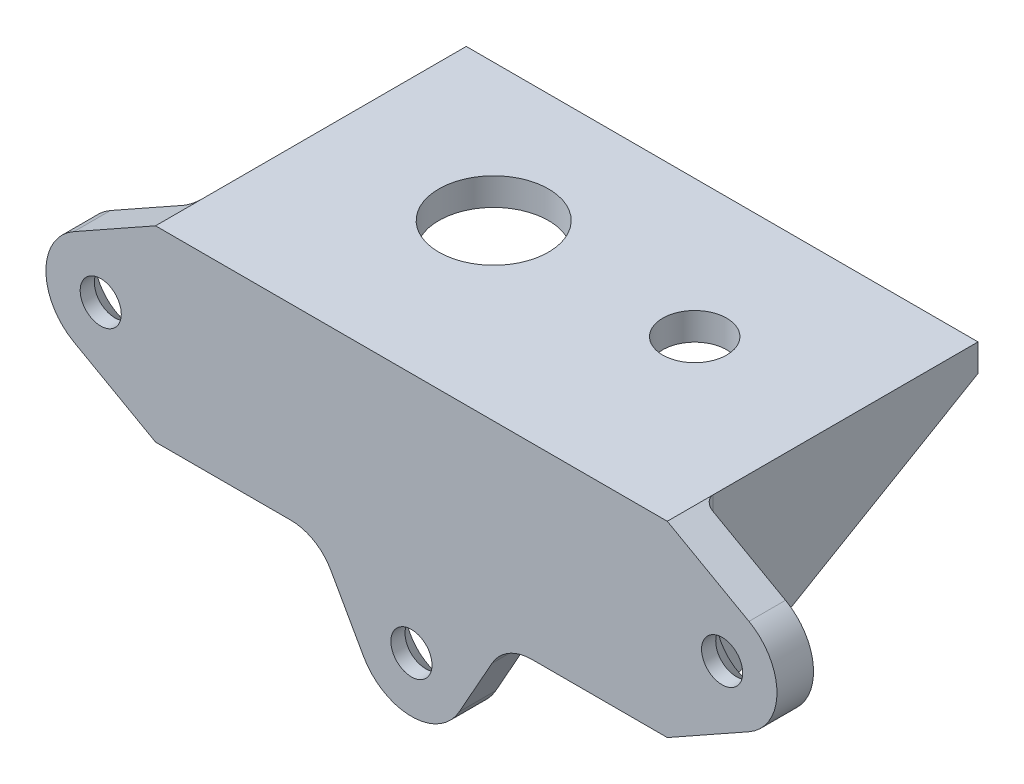
SolidWorks part; units mm, degrees
ref_plane "Front Plane" through (0, 0, 0) normal (0, 0, 1) x (1, 0, 0)
ref_plane "Top Plane" through (0, 0, 0) normal (0, 1, 0) x (1, 0, 0)
ref_plane "Right Plane" through (0, 0, 0) normal (1, 0, 0) x (0, 0, -1)
sketch "Sketch1" plane through (0, 0, 0) normal (0, 1, 0) x (1, 0, 0)
  line L0 (-10, 0) -> (12, 0) construction
  line L1 (-25, 15) -> (25, 15)
  line L2 (-25, 15) -> (-25, -15)
  line L3 (-25, -15) -> (25, -15)
  line L4 (25, 15) -> (25, -15)
  line L5 (-25, 15) -> (25, -15) construction
  line L6 (-25, -15) -> (25, 15) construction
  line L8 (-18.035, 14.545) -> (-1.965, 14.545) construction
  line L9 (-18.035, 14.545) -> (-18.035, -14.545) construction
  line L10 (-18.035, -14.545) -> (-1.965, -14.545) construction
  line L11 (-1.965, 14.545) -> (-1.965, -14.545) construction
  line L12 (-18.035, 14.545) -> (-1.965, -14.545) construction
  line L13 (-18.035, -14.545) -> (-1.965, 14.545) construction
  circle A0 centre (-10, 0) radius 6
  circle A1 centre (12, 0) radius 3.5
  circle A2 centre (12, 0) radius 8.5 construction
  point P0 (0, 0)
  dimension "D2" = 12
  dimension "D3" = 7
  dimension "D4" = 17
  dimension "D1" = 30
  dimension "D5" = 16.07
  dimension "D6" = 29.09
  dimension "D7" = 10
  dimension "D8" = 12
  dimension "D9" = 50
extrude "Boss-Extrude1" add sketch "Sketch1" along normal blind 3
sketch "Sketch2" plane through (0, 0, 15) normal (0, 0, 1) x (1, 0, 0)
  line L0 (-25, 0) -> (25, 0) construction
  line L1 (-25, 3) -> (25, 3)
  line L2 (-25, 3) -> (-25, -17.5)
  line L3 (-25, -17.5) -> (25, -17.5)
  line L4 (25, 3) -> (25, -17.5)
  line L5 (-25, 3) -> (25, -17.5) construction
  line L6 (-25, -17.5) -> (25, 3) construction
  point P4 (0, -7.25)
  dimension "D1" = 17.5
extrude "Boss-Extrude2" add sketch "Sketch2" along normal blind 4
sketch "Sketch3" plane through (-25, 0, 0) normal (-1, 0, 0) x (0, 0, 1)
  line L0 (-15, 3) -> (-15, 0)
  line L1 (-15, 0) -> (15, -17.5)
  line L2 (15, -17.5) -> (19, -17.5)
  line L3 (19, -17.5) -> (19, 3)
  line L4 (19, 3) -> (-15, 3)
extrude "Boss-Extrude3" add sketch "Sketch3" along normal blind 3
extrude "Boss-Extrude4" add sketch "Sketch3<2>" against normal blind 3 from surface starting at face at (25, -4.8333, 6.3333)
sketch "Sketch3<2>" plane through (-25, 0, 0) normal (-1, 0, 0) x (0, 0, 1) same geometry as "Sketch3"
sketch "Sketch5" plane through (0, 0, 19) normal (0, 0, 1) x (1, 0, 0)
  line L0 (0, 0) -> (0, -50000) construction
  line L1 (-28, 3) -> (-36.9375, -2.0183)
  line L2 (28, 3) -> (36.9375, -2.0183)
  line L3 (-36.9375, -12.4817) -> (-28, -17.5)
  line L4 (36.9375, -12.4817) -> (28, -17.5)
  line L5 (10.25, -17.5) -> (-10.25, -17.5)
  line L6 (-28, 3) -> (-28, -17.5)
  line L7 (28, 3) -> (28, -17.5)
  line L8 (-25, -17.5) -> (25, -17.5) construction
  line L9 (-10.25, -17.5) -> (-5.2317, -26.4375)
  line L10 (5.2317, -26.4375) -> (10.25, -17.5)
  arc A0 (-36.9375, -2.0183) -> (-36.9375, -12.4817) centre (-34, -7.25) ccw
  arc A1 (36.9375, -2.0183) -> (36.9375, -12.4817) centre (34, -7.25) cw
  arc A2 (-5.2317, -26.4375) -> (5.2317, -26.4375) centre (0, -23.5) ccw
  point P15 (-28, -7.25)
  point P16 (28, -7.25)
  point P22 (0, -17.5)
  dimension "D1" = 6
  dimension "D2" = 6
extrude "Boss-Extrude5" add sketch "Sketch5" against normal blind 4
sketch "Sketch6" plane through (0, 0, 15) normal (0, 0, -1) x (-1, 0, 0)
  point P0 (-34, -7.25)
  point P1 (34, -7.25)
  point P5 (0, -23.5)
hole_wizard "CSK for M4 Flat Head Machine Screw1" positions "Sketch6" profile "Sketch7" countersink size "M4" standard "ANSI Metric"
sketch "Sketch7" plane through (34, -7.25, 15) normal (1, 0, 0) x (0, 1, 0)
  line L0 (0, 0) -> (0, 11.3519)
  line L1 (0, 11.3519) -> (2.25, 10)
  line L2 (2.25, 10) -> (2.25, 2.45)
  line L3 (2.25, 2.45) -> (4.7, 0)
  line L5 (4.7, 0) -> (0, 0)
  line L6 (-2.25, 2.45) -> (-4.7, 0) construction
  line L10 (0, 11.3519) -> (-2.25, 10) construction
  line L11 (0, -6.35) -> (0, 107.95) construction
  dimension "Hole Dia." = 4.5
  dimension "Hole Depth" = 10
  dimension "Near C'Sink Dia." = 9.4
  dimension "Near C'Sink Angle" = 90
  dimension "Drill Angle" = 118
fillet "Fillet1" radius 5 2 edges at (-10.25, -17.5, 17) (10.25, -17.5, 17)
fillet "Fillet2" radius 1 7 edges at (-28, -7.25, 15) (28, -7.25, 15) (-25, 0, 0) (25, 0, 0) (25, -8.75, 15) (-25, -8.75, 15) (0, 0, 15)
